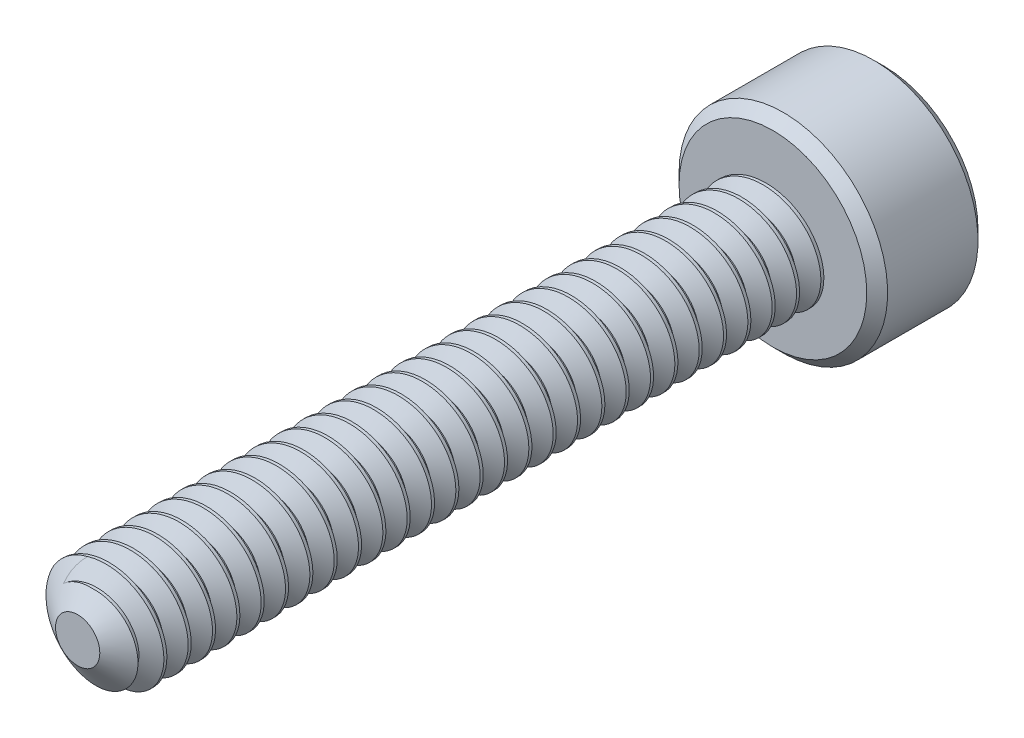
SolidWorks part; units mm, degrees
other "DetailItem1"
material "AISI 316 Stainless Steel Sheet (SS)"
ref_plane "Front Plane" through (0, 0, 0) normal (0, 0, 1) x (1, 0, 0)
ref_plane "Top Plane" through (0, 0, 0) normal (0, 1, 0) x (1, 0, 0)
ref_plane "Right Plane" through (0, 0, 0) normal (1, 0, 0) x (0, 0, -1)
sketch "Sketch1" plane through (0, 0, 0) normal (0, 0, 1) x (1, 0, 0)
  circle A0 centre (0, 0) radius 0.8
  dimension "OD" = 1.6
extrude "Extrude1" add sketch "Sketch1" against normal blind 10
sketch "Sketch2" plane through (0, 0, 0) normal (0, 0, 1) x (1, 0, 0)
  circle A0 centre (0, 0) radius 0.8 construction
  circle A1 centre (0, 0) radius 0.8
curve "Helix/Spiral1" pitch 0.35 height 10.35 turns 29.5714 parameters "pitch"=0.35
sketch "Sketch3" plane through (0, 0, 0) normal (1, 0, 0) x (0, 0, -1)
  line L0 (-0.3063, 0.8) -> (-0.175, 0.5727)
  line L1 (-0.175, 0.5727) -> (-0.1313, 0.5727)
  line L2 (-0.1313, 0.5727) -> (0, 0.8)
  line L3 (-0.3063, 0.8) -> (0, 0.8)
  line L4 (-0.1531, 0.8) -> (-0.1531, 0.5727) construction
  line L5 (-0.2406, 0.6863) -> (-0.0656, 0.6863) construction
  line L6 (0, 0.8) -> (0, -0.8) construction
  dimension "D1" = 0.0437
  dimension "D2" = 0.175
  dimension "D3" = 60
sweep "Cut-Sweep1" cut profiles "Sketch3" path "Helix/Spiral1" align with end faces yes
sketch "Sketch4" plane through (0, 0, 0) normal (1, 0, 0) x (0, 0, -1)
  line L0 (0.337, 0.8) -> (0, 0.3187)
  line L1 (0, 0.3187) -> (0, 0.8)
  line L2 (0.337, 0.8) -> (0, 0.8)
  line L3 (-0.3063, 0.8) -> (0, 0.8) construction
  line L4 (0, 0) -> (7.0209, 0) construction
  dimension "D1" = 55
  dimension "D2" = 0.254
revolve "Cut-Revolve1" cut sketch "Sketch4" angle 360 about L4
sketch "Sketch6" plane through (0, 0, -10) normal (0, 0, -1) x (-1, 0, 0)
  circle A0 centre (0, 0) radius 1.5
  dimension "head dia" = 3
extrude "Extrude2" add sketch "Sketch6" along normal blind 1.6
sketch "Sketch7" plane through (0, 0, -11.6) normal (0, 0, -1) x (-1, 0, 0)
  line L1 (0, 0.866) -> (-0.75, 0.433)
  line L2 (-0.75, 0.433) -> (-0.75, -0.433)
  line L3 (-0.75, -0.433) -> (0, -0.866)
  line L4 (0, -0.866) -> (0.75, -0.433)
  line L5 (0.75, -0.433) -> (0.75, 0.433)
  line L6 (0.75, 0.433) -> (0, 0.866)
  circle A0 centre (0, 0) radius 0.75 construction
  dimension "hex dia" = 1.5
extrude "Cut-Extrude1" cut sketch "Sketch7" against normal blind 1.125
sketch "Sketch8" plane through (0, 0, -11.6) normal (0, 0, -1) x (-1, 0, 0)
  circle A0 centre (0, 0) radius 0.866
extrude "Cut-Extrude2" cut sketch "Sketch8" against normal through all draft 45
chamfer "Chamfer1" distance 0.15 angle 45 2 edges at (-1.5, 0, -11.6) (-1.5, 0, -10)
sketch "Sketch10" plane through (0, 0, -10) normal (0, 0, 1) x (1, 0, 0)
  circle A1 centre (0, 0) radius 0.8
  circle A2 centre (0, 0) radius 0.8
  dimension "D1" = 0
ref_plane "Plane1" through (0, 0, 0) normal (0, 0, 1) x (1, 0, 0)
extrude "partial thread" [suppressed] add sketch "Sketch10" along normal up to surface (36 mm away) separate body
chamfer "Chamfer2" [suppressed] distance 0.032 angle 45
combine bodies "Combine1" [suppressed] operation type add bodies to combine 107 108
sketch "Sketch9" plane through (0, 0, 0) normal (1, 0, 0) x (0, 0, -1)
  line L0 (0, 0.8) -> (0, -0.8) construction
  line L1 (0.875, 0.8) -> (0.875, -0.8) construction
  dimension "D1" = 0.875
equation "\"D3@Helix/Spiral1\" = \"screw length@Extrude1\"+\"pitch@Helix/Spiral1\""
equation "\"D1@Sketch3\" = \"pitch@Helix/Spiral1\"*.125"
equation "\"D2@Sketch3\" = \"pitch@Helix/Spiral1\"*.5"
equation "\"D1@Cut-Extrude1\" = \"hex dia@Sketch7\"*.75"
equation "\"D1@Chamfer1\" = \"head dia@Sketch6\"*.05"
equation "\"D1@Sketch9\" = \"pitch@Helix/Spiral1\"*2.5"
equation "\"D1@Chamfer2\"=\"OD@Sketch1\"*.02"
